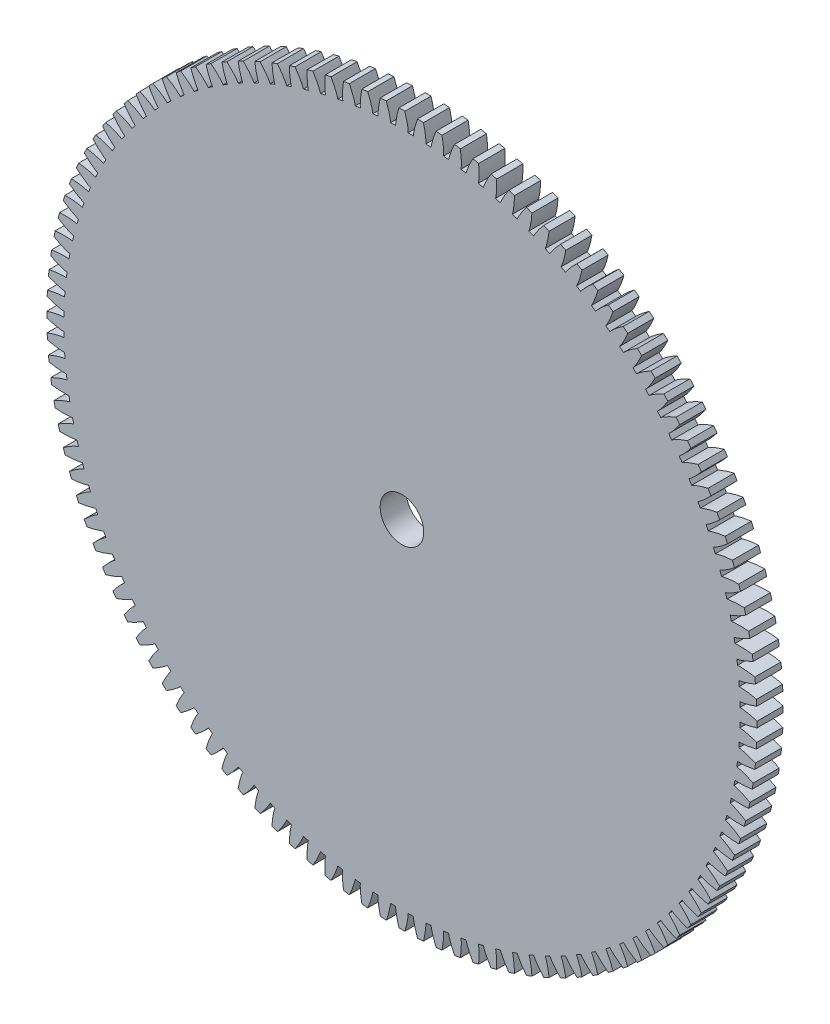
SolidWorks part; units mm, degrees
other "HARMONIC_PMI_surface_bore"
material "Brass"
ref_plane "Front Plane" through (0, 0, 0) normal (0, 0, 1) x (1, 0, 0)
ref_plane "Top Plane" through (0, 0, 0) normal (0, 1, 0) x (1, 0, 0)
ref_plane "Right Plane" through (0, 0, 0) normal (1, 0, 0) x (0, 0, -1)
sketch "Sketch1" plane through (0, 0, 0) normal (0, 0, 1) x (1, 0, 0)
  circle A0 centre (0, 0) radius 40.7737
  dimension "D1" = 81.5474
extrude "Boss-Extrude1" add sketch "Sketch1" along normal blind 3
sketch "Sketch2" plane through (0, 0, 0) normal (0, 0, 1) x (1, 0, 0)
  spline S0 degree 4 poles (38.8211, 0.7235) (38.8293, 0.7236) (38.845, 0.7235) (38.8706, 0.7229) (38.921, 0.7208) (38.9782, 0.7173) (39.0429, 0.7121) (39.1126, 0.7052) (39.1722, 0.6986) (39.2318, 0.6913) (39.2913, 0.6834) (39.3635, 0.673) (39.4502, 0.6596) (39.5519, 0.6423) (39.6675, 0.6208) (39.7857, 0.597) (39.9023, 0.5719) (40.0206, 0.5447) (40.1353, 0.5171) (40.2549, 0.4864) (40.3656, 0.4571) (40.4902, 0.4222) (40.5908, 0.3933) (40.7242, 0.353) (40.8032, 0.3284) (40.8959, 0.2989) (40.9371, 0.2854) (40.9625, 0.277) knots 0 0 0 0 0 0.015084 0.028532 0.04661 0.092111 0.119476 0.146842 0.174209 0.201575 0.228941 0.256307 0.307035 0.361767 0.4165 0.471232 0.525964 0.580697 0.635429 0.690161 0.744894 0.799626 0.854358 0.909091 0.954545 1 1 1 1 1 construction
  spline S1 degree 4 poles (38.8211, 0.7235) (38.8293, 0.7236) (38.845, 0.7235) (38.8706, 0.7229) (38.921, 0.7208) (38.9782, 0.7173) (39.0429, 0.7121) (39.1126, 0.7052) (39.1722, 0.6986) (39.2318, 0.6913) (39.2913, 0.6834) (39.3635, 0.673) (39.4502, 0.6596) (39.5519, 0.6423) (39.6675, 0.6208) (39.7857, 0.597) (39.9023, 0.5719) (40.0206, 0.5447) (40.1353, 0.5171) (40.2549, 0.4864) (40.3656, 0.4571) (40.4902, 0.4222) (40.5908, 0.3933) (40.6953, 0.3617) (40.7462, 0.346) (40.7723, 0.3379) knots 0 0 0 0 0 0.015084 0.028532 0.04661 0.092111 0.119476 0.146842 0.174209 0.201575 0.228941 0.256307 0.307035 0.361767 0.4165 0.471232 0.525964 0.580697 0.635429 0.690161 0.744894 0.799626 0.854358 0.909091 0.909091 0.909091 0.909091 0.909091
  spline S2 degree 4 poles (38.8057, 1.3092) (38.814, 1.3096) (38.8296, 1.3105) (38.8551, 1.3124) (38.9054, 1.3171) (38.9623, 1.3236) (39.0266, 1.3323) (39.0959, 1.3427) (39.1551, 1.3525) (39.2143, 1.3629) (39.2732, 1.3739) (39.3448, 1.388) (39.4307, 1.406) (39.5313, 1.4286) (39.6456, 1.456) (39.7624, 1.486) (39.8776, 1.5172) (39.9942, 1.5505) (40.1074, 1.5841) (40.2252, 1.621) (40.3342, 1.6561) (40.4568, 1.6975) (40.5558, 1.7316) (40.6869, 1.7789) (40.7645, 1.8075) (40.8555, 1.8418) (40.896, 1.8575) (40.9209, 1.8672) knots 0 0 0 0 0 0.015084 0.028532 0.04661 0.092111 0.119476 0.146842 0.174209 0.201575 0.228941 0.256307 0.307035 0.361767 0.4165 0.471232 0.525964 0.580697 0.635429 0.690161 0.744894 0.799626 0.854358 0.909091 0.954545 1 1 1 1 1 construction
  spline S3 degree 4 poles (38.8057, 1.3092) (38.814, 1.3096) (38.8296, 1.3105) (38.8551, 1.3124) (38.9054, 1.3171) (38.9623, 1.3236) (39.0266, 1.3323) (39.0959, 1.3427) (39.1551, 1.3525) (39.2143, 1.3629) (39.2732, 1.3739) (39.3448, 1.388) (39.4307, 1.406) (39.5313, 1.4286) (39.6456, 1.456) (39.7624, 1.486) (39.8776, 1.5172) (39.9942, 1.5505) (40.1074, 1.5841) (40.2252, 1.621) (40.3342, 1.6561) (40.4568, 1.6975) (40.5558, 1.7316) (40.6585, 1.7686) (40.7085, 1.7869) (40.7341, 1.7964) knots 0 0 0 0 0 0.015084 0.028532 0.04661 0.092111 0.119476 0.146842 0.174209 0.201575 0.228941 0.256307 0.307035 0.361767 0.4165 0.471232 0.525964 0.580697 0.635429 0.690161 0.744894 0.799626 0.854358 0.909091 0.909091 0.909091 0.909091 0.909091
  spline S4 degree 1 poles (40.7723, 0.3379) (59.9979, 0.4973) knots 0 0 1 1 construction
  spline S5 degree 1 poles (40.7723, 0.3379) (59.9979, 0.4973) knots 0 0 1 1
  spline S6 degree 4 poles (59.9993, 0.2811) (59.9993, 0.2966) (59.9991, 0.3264) (59.9989, 0.3667) (59.9981, 0.4759) (59.9977, 0.5237) (59.9964, 0.6646) (59.9954, 0.7445) (59.9939, 0.8601) (59.9924, 0.9543) (59.9907, 1.0614) (59.9888, 1.1607) (59.9867, 1.2646) (59.9845, 1.3658) (59.9821, 1.4686) (59.9795, 1.5706) (59.9767, 1.6727) (59.9738, 1.7754) (59.9707, 1.8766) (59.9673, 1.9805) (59.964, 2.0797) (59.9601, 2.1868) (59.9567, 2.2809) (59.9521, 2.3964) (59.949, 2.4763) (59.9429, 2.6171) (59.9408, 2.6648) (59.9359, 2.7739) (59.934, 2.8142) (59.9326, 2.844) (59.9318, 2.8594) knots 0 0 0 0 0 0.020959 0.041918 0.083333 0.123016 0.162698 0.202381 0.242063 0.281746 0.321429 0.361111 0.400794 0.440476 0.480159 0.519841 0.559524 0.599206 0.638889 0.678571 0.718254 0.757937 0.797619 0.837302 0.876984 0.916667 0.958082 0.979041 1 1 1 1 1 construction
  spline S7 degree 4 poles (59.9979, 0.4973) (59.9978, 0.5186) (59.9974, 0.5601) (59.9964, 0.6646) (59.9954, 0.7445) (59.9939, 0.8601) (59.9924, 0.9543) (59.9907, 1.0614) (59.9888, 1.1607) (59.9867, 1.2646) (59.9845, 1.3658) (59.9821, 1.4686) (59.9795, 1.5706) (59.9767, 1.6727) (59.9738, 1.7754) (59.9707, 1.8766) (59.9673, 1.9805) (59.964, 2.0797) (59.9601, 2.1868) (59.9567, 2.2809) (59.9521, 2.3964) (59.949, 2.4763) (59.9445, 2.5807) (59.9427, 2.6222) (59.9417, 2.6435) knots 0.083333 0.083333 0.083333 0.083333 0.083333 0.123016 0.162698 0.202381 0.242063 0.281746 0.321429 0.361111 0.400794 0.440476 0.480159 0.519841 0.559524 0.599206 0.638889 0.678571 0.718254 0.757937 0.797619 0.837302 0.876984 0.916667 0.916667 0.916667 0.916667 0.916667
  spline S8 degree 1 poles (59.9417, 2.6435) (40.7341, 1.7964) knots 0 0 1 1 construction
  spline S9 degree 1 poles (59.9417, 2.6435) (40.7341, 1.7964) knots 0 0 1 1
  spline S10 degree 1 poles (38.8057, 1.3092) (38.8211, 0.7235) knots 0 0 1 1 construction
  spline S11 degree 1 poles (38.8057, 1.3092) (38.8211, 0.7235) knots 0 0 1 1
extrude "Cut-Extrude2" cut sketch "Sketch2" against normal blind 4 and the other way blind 4
ref_axis "Axis1" through (0, 0, -0.15) along (0, 0, 1)
pattern_circular "CirPattern1" count 120 over 360 about axis through (0, 0, -0.15) along (0, 0, 1) of "Cut-Extrude2"
sketch "BoreProfile" plane through (0, 0, 0) normal (0, 0, 1) x (1, 0, 0)
  circle A0 centre (0, 0) radius 2.5
extrude "Bore" cut sketch "BoreProfile" against normal blind 5 and the other way blind 5
ref_axis "Axis2" through (0, 0, -0.15) along (0, 0, 1)
equation "\"FaceWidth\"= 3.0mm"
equation "\"BoreDia\"= 5.0mm"
equation "\"BoreDia@BoreProfile\" = \"BoreDia\""
